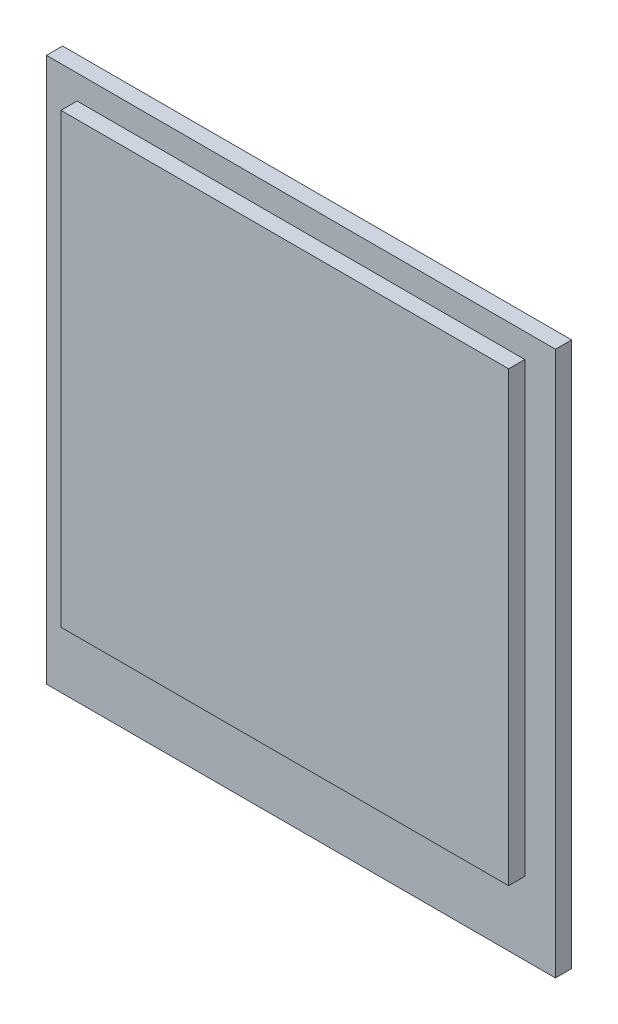
SolidWorks part; units mm, degrees
ref_plane "前视基准面" through (0, 0, 0) normal (0, 0, 1) x (1, 0, 0)
ref_plane "上视基准面" through (0, 0, 0) normal (0, 1, 0) x (1, 0, 0)
ref_plane "右视基准面" through (0, 0, 0) normal (1, 0, 0) x (0, 0, -1)
sketch "草图1" plane through (0, 0, 0) normal (0, 0, 1) x (1, 0, 0)
  line L0 (-17.2784, 0) -> (19.3294, 0) construction
  line L1 (0, 18.0553) -> (0, -16.6879) construction
  line L2 (-13.86, 13.86) -> (-13.86, -13.86)
  line L3 (-13.86, -13.86) -> (13.86, -13.86)
  line L4 (13.86, -13.86) -> (13.86, 13.86)
  line L5 (13.86, 13.86) -> (-13.86, 13.86)
  line L6 (-15.76, 15.36) -> (-15.76, -18.36)
  line L7 (-15.76, -18.36) -> (15.76, -18.36)
  line L8 (15.76, -18.36) -> (15.76, 15.36)
  line L9 (15.76, 15.36) -> (-15.76, 15.36)
  dimension "D1" = 27.72
  dimension "D2" = 27.72
  dimension "D3" = 31.52
  dimension "D4" = 33.72
  dimension "D5" = 1.5
extrude "凸台-拉伸1" add sketch "草图1" along normal blind 1 and the other way blind 1 contours L5 L2 L3 L4
extrude "凸台-拉伸3" add sketch "草图1<5>" against normal blind 1
sketch "草图1<5>" plane through (0, 0, 0) normal (0, 0, 1) x (1, 0, 0) same geometry as "草图1"
